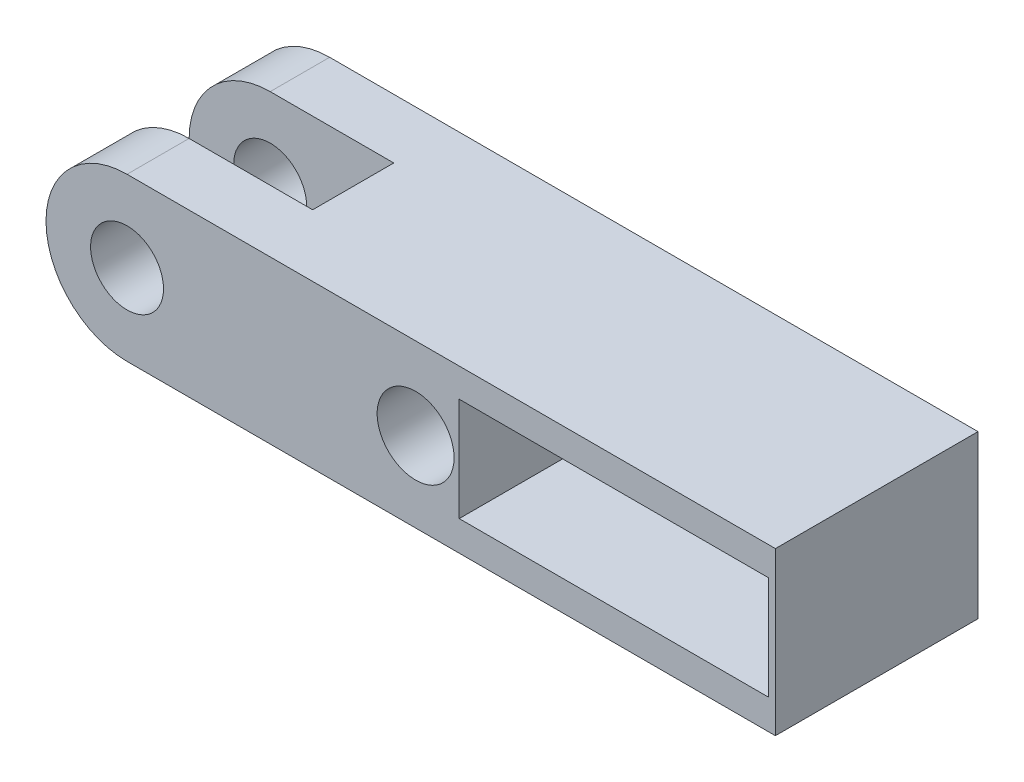
SolidWorks part; units mm, degrees
ref_plane "Front Plane" through (0, 0, 0) normal (0, 0, 1) x (1, 0, 0)
ref_plane "Top Plane" through (0, 0, 0) normal (0, 1, 0) x (1, 0, 0)
ref_plane "Right Plane" through (0, 0, 0) normal (1, 0, 0) x (0, 0, -1)
sketch "Sketch1" plane through (0, 0, 0) normal (0, 0, 1) x (1, 0, 0)
  line L1 (0, 5) -> (40, 5)
  line L2 (0, -5) -> (40, -5)
  line L3 (40, 5) -> (40, -5)
  line L4 (40, -5) -> (31.6243, -5)
  line L5 (20.4939, 3.2292) -> (39.5739, 3.2292)
  line L6 (20.4939, 3.2292) -> (20.4939, -3.1508)
  line L7 (20.4939, -3.1508) -> (39.5739, -3.1508)
  line L8 (39.5739, 3.2292) -> (39.5739, -3.1508)
  arc A0 (0, 5) -> (0, -5) centre (0, 0) ccw
  circle A2 centre (0, 0) radius 2.25
  circle A4 centre (17.8029, -0.0668) radius 2.3727
  dimension "D1" = 5
  dimension "D3" = 4.5
  dimension "D2" = 40
  dimension "D4" = 10
extrude "Boss-Extrude1" add sketch "Sketch1" along normal mid plane 12.5 contours L2 | L1 A0 L2 L3 A2 region at (13.896, -0.0127, 0)
sketch "Sketch13" plane through (0, -5, 0) normal (0, -1, 0) x (1, 0, 0)
  line L1 (-5.2437, -2.5815) -> (7.6238, -2.5815)
  line L2 (-5.2437, -2.5815) -> (-5.2437, 2.4226)
  line L3 (-5.2437, 2.4226) -> (7.6238, 2.4226)
  line L4 (7.6238, -2.5815) -> (7.6238, 2.4226)
extrude "Cut-Extrude1" cut sketch "Sketch13" against normal blind 10
chamfer "Chamfer1" distance 10 angle 45 1 edges at (7.6238, -5, -0.0794) tangent propagation no
